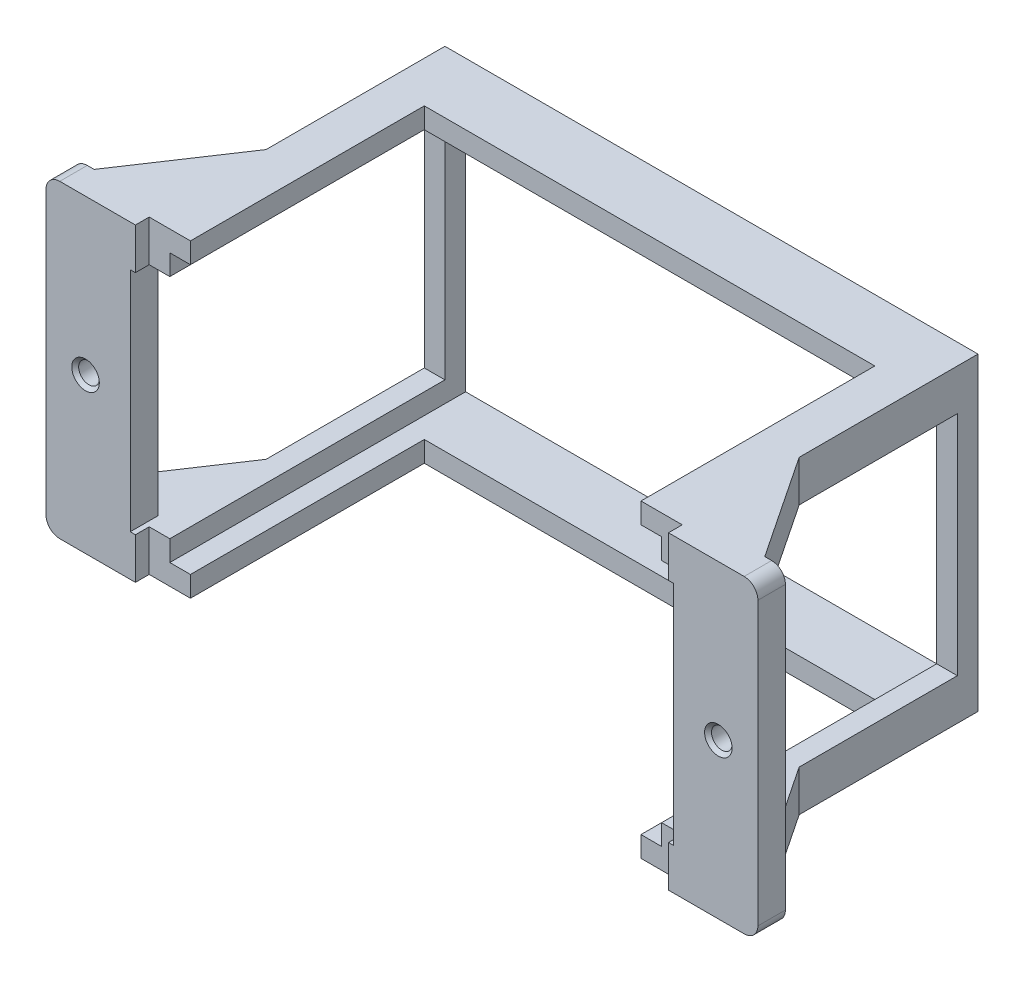
SolidWorks part; units mm, degrees
ref_plane "前视基准面" through (0, 0, 0) normal (0, 0, 1) x (1, 0, 0)
ref_plane "上视基准面" through (0, 0, 0) normal (0, 1, 0) x (1, 0, 0)
ref_plane "右视基准面" through (0, 0, 0) normal (1, 0, 0) x (0, 0, -1)
sketch "草图1" plane through (0, 0, 0) normal (0, 0, 1) x (1, 0, 0)
  line L0 (-38.75, 22.5) -> (38.75, 22.5)
  line L1 (-35.75, 19.5) -> (35.75, 19.5)
  line L2 (-35.75, 19.5) -> (-35.75, -19.5)
  line L3 (-35.75, -19.5) -> (35.75, -19.5)
  line L4 (35.75, 19.5) -> (35.75, -19.5)
  line L5 (38.75, 22.5) -> (38.75, -22.5)
  line L6 (-38.75, -22.5) -> (38.75, -22.5)
  line L7 (-38.75, 22.5) -> (-38.75, -22.5)
  dimension "D1" = 71.5
  dimension "D2" = 35.75
  dimension "D3" = 39
  dimension "D4" = 19.5
  dimension "D5" = 3
extrude "凸台-拉伸1" add sketch "草图1" along normal blind 3
sketch "草图2" plane through (0, 0, 3) normal (0, 0, 1) x (1, 0, 0)
  line L0 (0, 0) -> (0, 50000) construction
  line L1 (38.75, 22.5) -> (35.75, 22.5)
  line L2 (38.75, 22.5) -> (38.75, 19.5)
  line L3 (38.75, 19.5) -> (35.75, 19.5)
  line L4 (35.75, 22.5) -> (35.75, 19.5)
  line L5 (0, 0) -> (50000, 0) construction
  line L6 (-35.75, 22.5) -> (-35.75, 19.5)
  line L7 (-38.75, 19.5) -> (-35.75, 19.5)
  line L8 (-38.75, 22.5) -> (-38.75, 19.5)
  line L9 (-38.75, 22.5) -> (-35.75, 22.5)
  line L10 (-38.75, -22.5) -> (-35.75, -22.5)
  line L11 (-38.75, -22.5) -> (-38.75, -19.5)
  line L12 (-38.75, -19.5) -> (-35.75, -19.5)
  line L13 (-35.75, -22.5) -> (-35.75, -19.5)
  line L14 (35.75, -22.5) -> (35.75, -19.5)
  line L15 (38.75, -19.5) -> (35.75, -19.5)
  line L16 (38.75, -22.5) -> (38.75, -19.5)
  line L17 (38.75, -22.5) -> (35.75, -22.5)
extrude "凸台-拉伸2" add sketch "草图2" along normal blind 40
sketch "草图3" plane through (0, 0, 3) normal (0, 0, 1) x (1, 0, 0)
  line L0 (38.75, -19.5) -> (38.75, 19.5) construction
  line L1 (35.75, 19.5) -> (38.75, 19.5)
  line L2 (35.75, 19.5) -> (35.75, 16.5)
  line L3 (35.75, 16.5) -> (38.75, 16.5)
  line L4 (38.75, 19.5) -> (38.75, 16.5)
  line L5 (35.75, 22.5) -> (-35.75, 22.5) construction
  line L6 (35.75, 19.5) -> (32.75, 19.5)
  line L7 (35.75, 19.5) -> (35.75, 22.5)
  line L8 (35.75, 22.5) -> (32.75, 22.5)
  line L9 (32.75, 19.5) -> (32.75, 22.5)
  line L10 (0, 0) -> (0, 50000) construction
  line L11 (0, 0) -> (50000, 0) construction
  line L12 (-32.75, 19.5) -> (-32.75, 22.5)
  line L13 (-35.75, 22.5) -> (-32.75, 22.5)
  line L14 (-35.75, 19.5) -> (-35.75, 22.5)
  line L15 (-35.75, 19.5) -> (-32.75, 19.5)
  line L16 (-38.75, 19.5) -> (-38.75, 16.5)
  line L17 (-35.75, 16.5) -> (-38.75, 16.5)
  line L18 (-35.75, 19.5) -> (-35.75, 16.5)
  line L19 (-35.75, 19.5) -> (-38.75, 19.5)
  line L20 (-35.75, -19.5) -> (-38.75, -19.5)
  line L21 (-35.75, -19.5) -> (-35.75, -16.5)
  line L22 (-35.75, -16.5) -> (-38.75, -16.5)
  line L23 (-38.75, -19.5) -> (-38.75, -16.5)
  line L24 (-35.75, -19.5) -> (-32.75, -19.5)
  line L25 (-35.75, -19.5) -> (-35.75, -22.5)
  line L26 (-35.75, -22.5) -> (-32.75, -22.5)
  line L27 (-32.75, -19.5) -> (-32.75, -22.5)
  line L28 (32.75, -19.5) -> (32.75, -22.5)
  line L29 (35.75, -22.5) -> (32.75, -22.5)
  line L30 (35.75, -19.5) -> (35.75, -22.5)
  line L31 (35.75, -19.5) -> (32.75, -19.5)
  line L32 (38.75, -19.5) -> (38.75, -16.5)
  line L33 (35.75, -16.5) -> (38.75, -16.5)
  line L34 (35.75, -19.5) -> (35.75, -16.5)
  line L35 (35.75, -19.5) -> (38.75, -19.5)
  line M5 (35.75, 19.5) -> (35.75, -19.5)
  line M6 (35.75, -19.5) -> (38.75, -19.5)
  line M7 (38.75, -19.5) -> (38.75, 19.5)
  line M8 (38.75, 19.5) -> (35.75, 19.5)
  dimension "D1" = 3
  dimension "D2" = 3
extrude "凸台-拉伸3" add sketch "草图3" along normal blind 40 contours L23 L20 L21 L22 | L27 L24 L25 L26 | L30 L31 L28 L29 | L33 M5 M6 M7 | L3 M5 M7 M8 | L9 L6 L7 L8 | L14 L15 L12 L13 | L18 L19 L16 L17 region at (34.25, -21, 3) region at (37.25, 18, 3) region at (34.25, 21, 3) region at (37.25, -18, 3) region at (-34.25, 21, 3) region at (-37.25, 18, 3) region at (-37.25, -18, 3) region at (-34.25, -21, 3)
sketch "草图4" plane through (0, 0, 43) normal (0, 0, 1) x (1, 0, 0)
  line L0 (38.75, -22.5) -> (38.75, -16.5) construction
  line L1 (38.75, 22.5) -> (53.75, 22.5)
  line L2 (38.75, 22.5) -> (38.75, 16.5)
  line L3 (38.75, 16.5) -> (39.5, 16.5)
  line L6 (39.5, 16.5) -> (39.5, -16.5)
  line L9 (39.5, -16.5) -> (38.75, -16.5)
  line L10 (53.75, 22.5) -> (53.75, -22.5)
  line L11 (53.75, -22.5) -> (38.75, -22.5)
  line L12 (38.75, -16.5) -> (38.75, -22.5)
  line L13 (32.75, -22.5) -> (38.75, -22.5) construction
  line L14 (35.75, -16.5) -> (38.75, -16.5) construction
  line L15 (35.75, 16.5) -> (38.75, 16.5) construction
  line L16 (0, 0) -> (0, 50000) construction
  line L17 (-38.75, -16.5) -> (-38.75, -22.5)
  line L18 (-53.75, -22.5) -> (-38.75, -22.5)
  line L19 (-53.75, 22.5) -> (-53.75, -22.5)
  line L20 (-39.5, -16.5) -> (-38.75, -16.5)
  line L21 (-39.5, 16.5) -> (-39.5, -16.5)
  line L22 (-38.75, 16.5) -> (-39.5, 16.5)
  line L23 (-38.75, 22.5) -> (-38.75, 16.5)
  line L24 (-38.75, 22.5) -> (-53.75, 22.5)
  dimension "D1" = 39.5
  dimension "D2" = 15
extrude "凸台-拉伸4" add sketch "草图4" along normal blind 2 and the other way blind 2 separate body
sketch "草图5" plane through (0, 22.5, 0) normal (0, 1, 0) x (1, 0, 0)
  line L0 (32.75, -43) -> (32.75, -3) construction
  line L1 (32.75, -9) -> (-32.75, -9)
  line L2 (32.75, -9) -> (32.75, -3)
  line L3 (32.75, -3) -> (-32.75, -3)
  line L4 (-32.75, -9) -> (-32.75, -3)
  dimension "D1" = 6
extrude "凸台-拉伸5" add sketch "草图5" against normal blind 3
sketch "草图6" plane through (0, -22.5, 0) normal (0, -1, 0) x (1, 0, 0)
  line L4 (32.75, 9) -> (-32.75, 9)
  line L5 (-32.75, 9) -> (-32.75, 3)
  line L6 (-32.75, 3) -> (32.75, 3)
  line L7 (32.75, 3) -> (32.75, 9)
  line L8 (32.75, 9) -> (-32.75, 9)
  line L9 (-32.75, 9) -> (-32.75, 3)
  line L10 (-32.75, 3) -> (32.75, 3)
  line L11 (32.75, 3) -> (32.75, 9)
  dimension "D1" = 0
extrude "凸台-拉伸6" add sketch "草图6" against normal blind 3 separate body
sketch "草图7" plane through (0, 0, 45) normal (0, 0, 1) x (1, 0, 0)
  line L0 (0, 0) -> (0, 50000) construction
  circle A0 centre (-46, 0) radius 1.5
  circle A1 centre (46, 0) radius 1.5
  dimension "D1" = 46
  dimension "D2" = 3
extrude "切除-拉伸1" cut sketch "草图7" against normal blind 5
chamfer "倒角1" distance 0.5 angle 45 1 edges at (-44.5, 0, 45)
chamfer "倒角2" distance 0.5 angle 45 1 edges at (44.5, 0, 45)
chamfer "倒角3" distance 2 angle 45 2 edges at (53.75, -22.5, 43) (53.75, 22.5, 43)
combine bodies "组合1" operation type add bodies to combine 112 117
combine bodies "组合2" operation type add bodies to combine 113 118
combine bodies "组合3" operation type add bodies to combine 116 119
chamfer "倒角4" distance 2 angle 45 2 edges at (-53.75, -22.5, 43) (-53.75, 22.5, 43)
sketch "草图8" plane through (0, 22.5, 0) normal (0, 1, 0) x (1, 0, 0)
  line L0 (48.75, -41) -> (38.75, -26)
  line L1 (51.75, -41) -> (38.75, -41) construction
  line L2 (38.75, -41) -> (38.75, 0) construction
  line L3 (38.75, -26) -> (38.75, -41)
  line L4 (38.75, -41) -> (48.75, -41)
  line L5 (0, 0.5284) -> (0, 50000.5284) construction
  dimension "D1" = 10
  dimension "D2" = 15
extrude "凸台-拉伸7" add sketch "草图8" against normal blind 6
mirror "镜向1" about plane through (0, 0, 0) normal (1, 0, 0) of "凸台-拉伸7"
mirror "镜向2" about plane through (0, 0, 0) normal (0, 1, 0) of "镜向1"
sketch "草图9" plane through (0, 0, 41) normal (0, 0, -1) x (-1, 0, 0)
  line L0 (51.75, -22.5) -> (48.75, -22.5) construction
  line L1 (51.75, 22.5) -> (53.75, 22.5)
  line L2 (51.75, 22.5) -> (51.75, -22.5)
  line L3 (51.75, -22.5) -> (53.75, -22.5)
  line L4 (53.75, 22.5) -> (53.75, -22.5)
  line L5 (53.75, 20.5) -> (53.75, -20.5) construction
  line L6 (0, 0) -> (0, -50000) construction
  line L7 (-53.75, 22.5) -> (-53.75, -22.5)
  line L8 (-51.75, -22.5) -> (-53.75, -22.5)
  line L9 (-51.75, 22.5) -> (-51.75, -22.5)
  line L10 (-51.75, 22.5) -> (-53.75, 22.5)
extrude "切除-拉伸2" cut sketch "草图9" against normal blind 10
fillet "圆角1" radius 2 4 edges at (-51.75, 22.5, 43) (-51.75, -22.5, 43) (51.75, -22.5, 43) (51.75, 22.5, 43)
